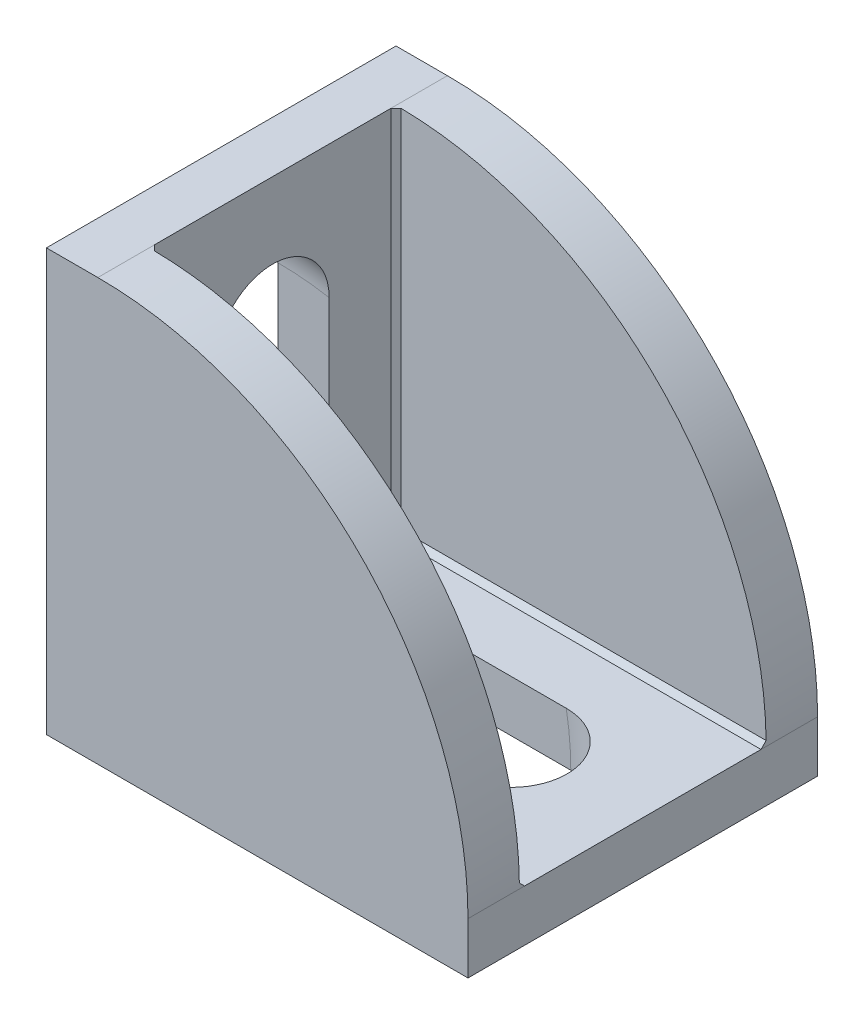
SolidWorks part; units mm, degrees
material "6063-O"
ref_plane "Ön Düzlem" through (0, 0, 0) normal (0, 0, 1) x (1, 0, 0)
ref_plane "Üst Düzlem" through (0, 0, 0) normal (0, 1, 0) x (1, 0, 0)
ref_plane "Sağ Düzlem" through (0, 0, 0) normal (1, 0, 0) x (0, 0, -1)
sketch "Çizim1" plane through (0, 0, 0) normal (0, 0, 1) x (1, 0, 0)
  line L0 (0, 0) -> (0, 20.5)
  line L1 (0, 20.5) -> (2.5, 20.5)
  line L2 (2.5, 20.5) -> (2.5, 2.5)
  line L3 (2.5, 2.5) -> (20.5, 2.5)
  line L4 (20.5, 2.5) -> (20.5, 0)
  line L5 (20.5, 0) -> (0, 0)
  dimension "D1" = 20.5
  dimension "D2" = 2.5
extrude "Yükseklik-Ekstrüzyon1" add sketch "Çizim1" along normal mid plane 17
sketch "Çizim2" plane through (0, 0, 8.5) normal (0, 0, 1) x (1, 0, 0)
  line L0 (20.5, 2.5) -> (2.5, 2.5) construction
  line L1 (2.5, 2.5) -> (2.5, 20.5) construction
  line L2 (20.5, 2.5) -> (2.5, 2.5)
  line L3 (2.5, 2.5) -> (2.5, 20.5)
  arc A0 (20.5, 2.5) -> (2.5, 20.5) centre (2.5, 2.5) ccw
extrude "Yükseklik-Ekstrüzyon2" add sketch "Çizim2" against normal blind 2.5
mirror "Aynalama1" about plane through (0, 0, 0) normal (0, 0, 1) of "Yükseklik-Ekstrüzyon2"
sketch "Çizim3" plane through (0, 0, 0) normal (1, 0, 0) x (0, 0, -1)
  line L0 (0, 8.75) -> (0, 14.25) construction
  line L1 (-2.75, 8.75) -> (-2.75, 14.25)
  line L2 (2.75, 8.75) -> (2.75, 14.25)
  line L4 (-6, 2.5) -> (6, 2.5) construction
  arc A0 (-2.75, 8.75) -> (2.75, 8.75) centre (0, 8.75) ccw
  arc A1 (2.75, 14.25) -> (-2.75, 14.25) centre (0, 14.25) ccw
  point P3 (0, 11.5)
  dimension "D1" = 5.5
  dimension "D2" = 5.5
  dimension "D3" = 9
revolve "Kes-Döndür1" cut sketch "Çizim3" angle 360 about axis through (0, 0, 8.5) along (0, 0, -1)
chamfer "Pah1" distance 0.25 angle 45 5 edges at (11.5, 2.5, 6) (11.5, 2.5, -6) (2.5, 11.5, -6) (2.5, 2.5, 0) (2.5, 11.5, 6)
